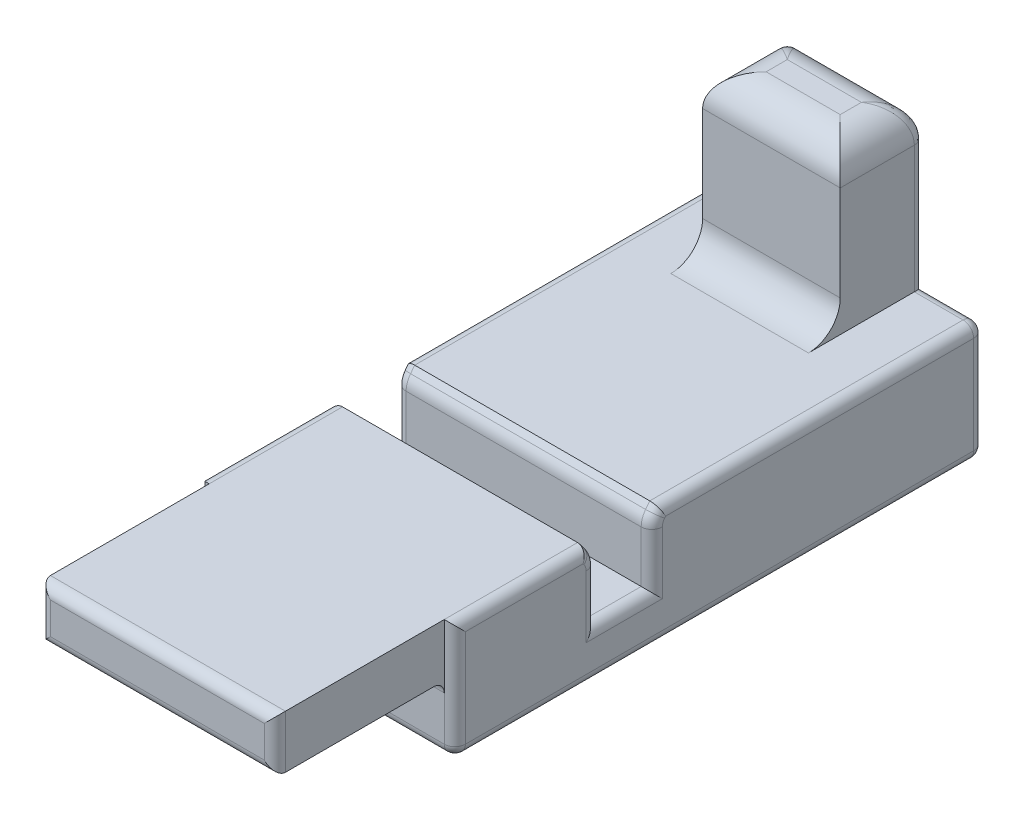
SolidWorks part; units mm, degrees
ref_plane "Front Plane" through (0, 0, 0) normal (0, 0, 1) x (1, 0, 0)
ref_plane "Top Plane" through (0, 0, 0) normal (0, 1, 0) x (1, 0, 0)
ref_plane "Right Plane" through (0, 0, 0) normal (1, 0, 0) x (0, 0, -1)
sketch "Sketch1" plane through (0, 0, 0) normal (0, 0, 1) x (1, 0, 0)
  line L15 (-29.4907, 17.9886) -> (-14.4907, 17.9886)
  line L25 (-14.4907, 17.9886) -> (-10.0907, 17.9886)
  line L26 (-10.0907, 17.9886) -> (-10.0907, 6.7886)
  line L27 (-10.0907, 6.7886) -> (-34.2907, 6.7886)
  line L28 (-34.2907, 6.7886) -> (-34.2907, 17.9886)
  line L29 (-34.2907, 17.9886) -> (-29.4907, 17.9886)
  dimension "D1" = 24.2
  dimension "D2" = 11.2
extrude "Boss-Extrude1" add sketch "Sketch1" against normal blind 50
sketch "Sketch2" plane through (-34.2907, 0, 0) normal (-1, 0, 0) x (0, 0, 1)
  line L0 (-16, 17.9886) -> (-16, 6.7886) construction
  line L1 (-50, 17.9886) -> (0, 17.9886) construction
  line L2 (-50, 6.7886) -> (0, 6.7886) construction
  line L3 (-50, 6.7886) -> (-50, 17.9886) construction
  line L4 (-18.6, 16.2601) -> (-18.6, 11.3886)
  line L8 (-13.4, 11.3886) -> (-18.6, 11.3886)
  line L10 (-19.5, 18.107) -> (-19.0178, 17.4835)
  line L12 (-13.4, 16.2601) -> (-13.4, 11.3886)
  line L13 (-12.5, 18.107) -> (-12.9822, 17.4835)
  line L15 (-19.5, 18.107) -> (-12.5, 18.107)
  line L16 (-50, 6.7886) -> (0, 6.7886) construction
  arc A0 (-18.6, 16.2601) -> (-19.0178, 17.4835) centre (-20.6, 16.2601) ccw
  arc A1 (-13.4, 16.2601) -> (-12.9822, 17.4835) centre (-11.4, 16.2601) cw
  point P13 (-16, 11.3886)
  point P17 (-16, 11.3886)
  dimension "D2" = 2
  dimension "D1" = 34
  dimension "D3" = 2.6
  dimension "D4" = 3.5
  dimension "D5" = 4.6
extrude "Cut-Extrude1" cut sketch "Sketch2" against normal through all
sketch "Sketch3" plane through (0, 17.9886, 0) normal (0, 1, 0) x (1, 0, 0)
  line L0 (-22.1907, 50) -> (-22.1907, 0) construction
  line L1 (-10.0907, 50) -> (-34.2907, 50) construction
  line L2 (-10.0907, 0) -> (-34.2907, 0) construction
  line L4 (-15.6907, 42) -> (-28.6907, 42)
  line L5 (-15.6907, 42) -> (-15.6907, 50)
  line L6 (-15.6907, 50) -> (-28.6907, 50)
  line L7 (-28.6907, 42) -> (-28.6907, 50)
  line L8 (-15.6907, 42) -> (-28.6907, 50) construction
  line L9 (-15.6907, 50) -> (-28.6907, 42) construction
  point P6 (-22.1907, 46)
  dimension "D1" = 13
  dimension "D2" = 8
extrude "Boss-Extrude2" add sketch "Sketch3" along normal blind 15
fillet "Fillet1" radius 3 5 edges at (-22.1907, 32.9886, -50) (-15.6907, 32.9886, -46) (-22.1907, 32.9886, -42) (-28.6907, 32.9886, -46) (-22.1907, 17.9886, -42)
fillet "Fillet2" radius 1 30 edges at (-16.5694, 32.1099, -49.1213) (-27.812, 32.1099, -49.1213) (-34.2907, 16.9065, -18.7073) (-34.2907, 13.8243, -18.6) (-34.2907, 11.3886, -16) (-34.2907, 13.8243, -13.4) (-34.2907, 16.9065, -13.2927) (-34.2907, 17.736, -12.7869) (-34.2907, 17.9886, -34.7042) (-34.2907, 12.3886, 0) (-34.2907, 17.736, -19.2131) (-34.2907, 6.7886, -25) (-22.1907, 6.7886, 0) (-10.0907, 17.9886, -34.7042) (-10.0907, 6.7886, -25) (-10.0907, 12.3886, 0) (-10.0907, 17.736, -12.7869) (-10.0907, 16.9065, -13.2927) (-10.0907, 13.8243, -13.4) (-10.0907, 11.3886, -16) (-10.0907, 13.8243, -18.6) (-10.0907, 16.9065, -18.7073) (-10.0907, 17.736, -19.2131) (-31.4907, 17.9886, -50) (-34.2907, 12.3886, -50) (-22.1907, 6.7886, -50) (-10.0907, 12.3886, -50) (-12.8907, 17.9886, -50) (-15.6907, 23.9886, -50) (-28.6907, 23.9886, -50)
sketch "Sketch4" plane through (0, 0, 0) normal (0, 0, 1) x (1, 0, 0)
  line L0 (-33.2907, 17.9886) -> (-33.2907, 7.7886) construction
  line L1 (-33.2907, 17.9886) -> (-11.0907, 17.9886)
  line L2 (-33.2907, 17.9886) -> (-33.2907, 12.9886)
  line L3 (-33.2907, 12.9886) -> (-11.0907, 12.9886)
  line L4 (-11.0907, 17.9886) -> (-11.0907, 12.9886)
  line L5 (-11.0907, 17.9886) -> (-33.2907, 17.9886) construction
  line L6 (-11.0907, 7.7886) -> (-11.0907, 17.9886) construction
  dimension "D1" = 5
extrude "Boss-Extrude3" add sketch "Sketch4" along normal blind 16
fillet "Fillet3" radius 1 5 edges at (-22.1907, 17.9886, 16) (-11.0907, 15.4886, 16) (-22.1907, 12.9886, 16) (-33.2907, 15.4886, 16) (-22.1907, 12.9886, 0)
